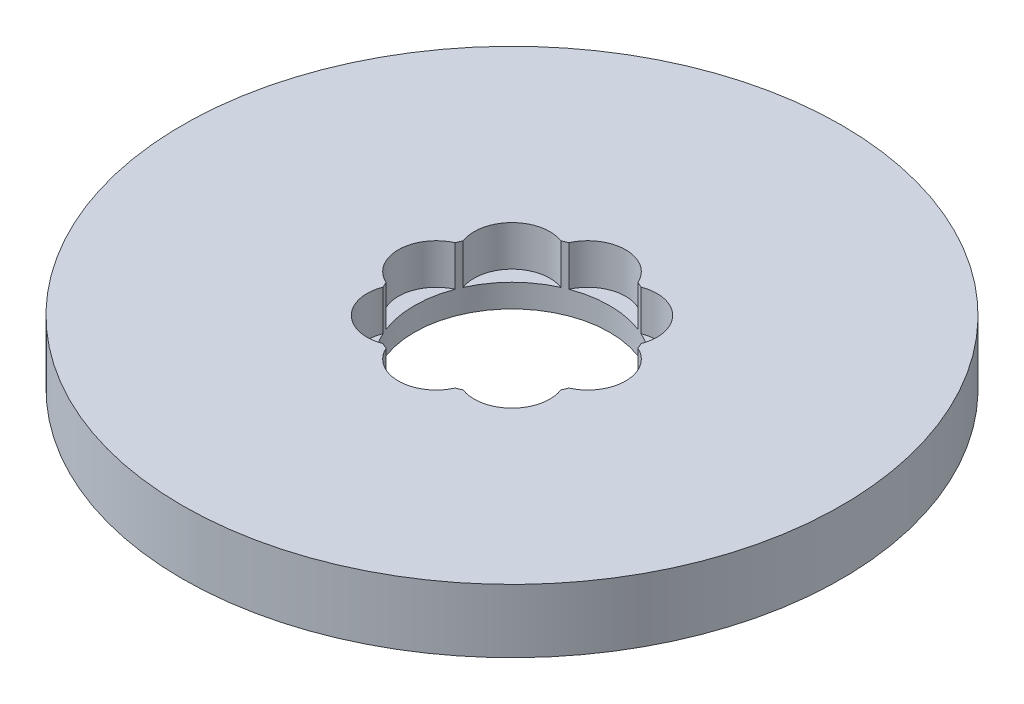
SolidWorks part; units mm, degrees
ref_plane "Front Plane" through (0, 0, 0) normal (0, 0, 1) x (1, 0, 0)
ref_plane "Top Plane" through (0, 0, 0) normal (0, 1, 0) x (1, 0, 0)
ref_plane "Right Plane" through (0, 0, 0) normal (1, 0, 0) x (0, 0, -1)
sketch "Sketch1" plane through (0, 0, 0) normal (0, 1, 0) x (1, 0, 0)
  circle A0 centre (0, 0) radius 67.5
  dimension "FLANGE_OD" = 135
extrude "Boss-Extrude1" add sketch "Sketch1" along normal blind 13
sketch "Sketch2" plane through (0, 0, 0) normal (0, 1, 0) x (1, 0, 0)
  circle A0 centre (0, 0) radius 20
  dimension "BORE_D" = 40
extrude "Cut-Extrude1" cut sketch "Sketch2" along normal through all
sketch "Sketch3" plane through (0, 13, 0) normal (0, 1, 0) x (1, 0, 0)
  circle A0 centre (0, 0) radius 15.5227 construction
  circle A1 centre (-15.5227, 0) radius 7.7586
  dimension "BOLT_D" = 15.5171
  dimension "BOLT_PCD" = 31.0454
extrude "Cut-Extrude2" cut sketch "Sketch3" against normal blind 8.2636
pattern_circular "CirPattern1" count 8 over 360 about axis through (0, 0, 0) along (0, 1, 0) of "Cut-Extrude2"
